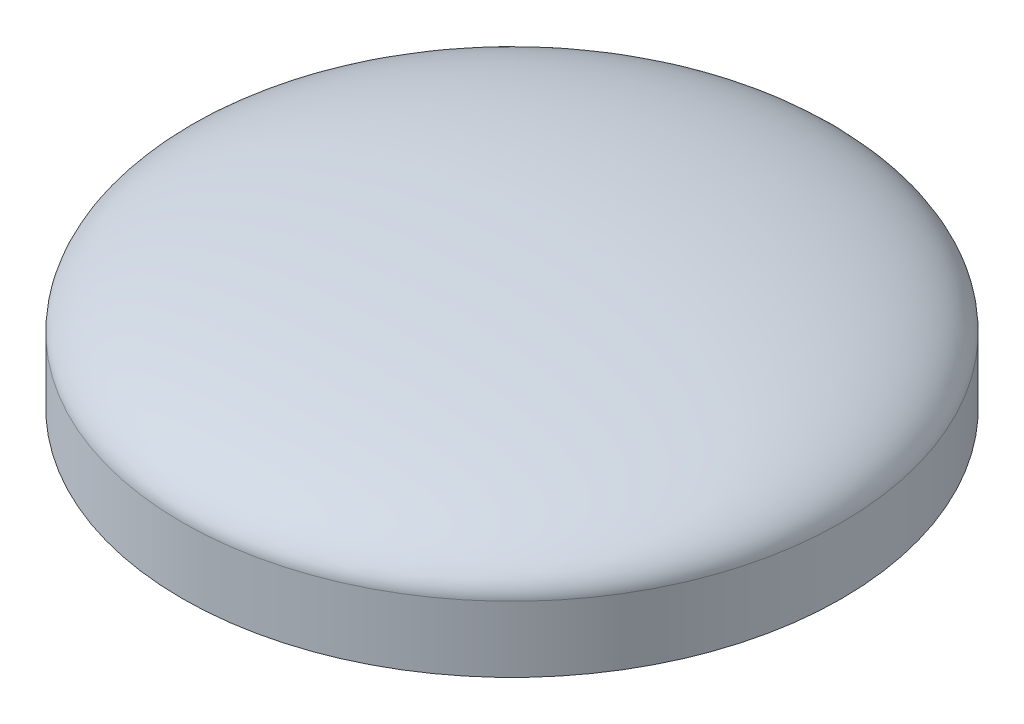
SolidWorks part; units mm, degrees
ref_plane "Front" through (0, 0, 0) normal (0, 0, 1) x (1, 0, 0)
ref_plane "Top" through (0, 0, 0) normal (0, 1, 0) x (1, 0, 0)
ref_plane "Right" through (0, 0, 0) normal (1, 0, 0) x (0, 0, -1)
sketch "Sketch1" plane through (0, 0, 0) normal (0, 1, 0) x (1, 0, 0)
  circle A0 centre (0, 0) radius 100
  dimension "D1" = 200
extrude "Boss-Extrude1" add sketch "Sketch1" along normal blind 20
sketch "Sketch2" plane through (0, 0, 0) normal (0, 0, 1) x (1, 0, 0)
  line L0 (0, 20) -> (0, 45)
  line L1 (0, 20) -> (-100, 20)
  line L2 (100, 20) -> (-100, 20) construction
  ellipse E0 centre (0, 20) end of major axis (-100, 20) minor radius 25 (0, 45) -> (-100, 20) ccw
  dimension "D1" = 45
revolve "Revolve1" add sketch "Sketch2" angle 360 about L0
shell "Shell1" thickness 2 removed face at (0, 0, 100)
ref_axis "Axis1" through (0, 50, 0) along (0, -1, 0)
